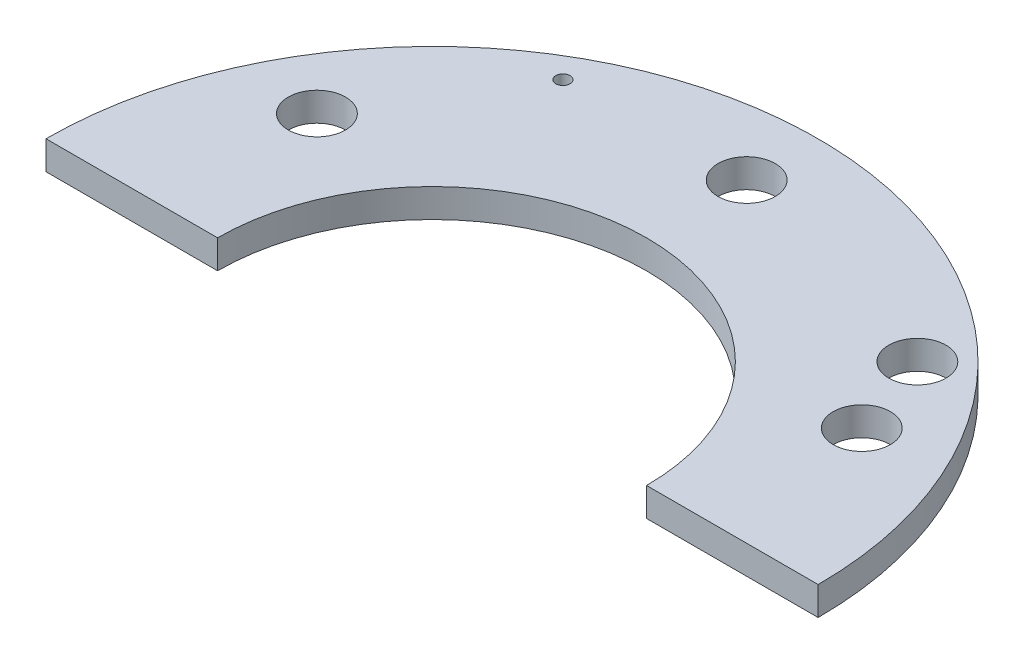
SolidWorks part; units mm, degrees
material "ABS"
ref_plane "Front Plane" through (0, 0, 0) normal (0, 0, 1) x (1, 0, 0)
ref_plane "Top Plane" through (0, 0, 0) normal (0, 1, 0) x (1, 0, 0)
ref_plane "Right Plane" through (0, 0, 0) normal (1, 0, 0) x (0, 0, -1)
sketch "Sketch1" plane through (0, 0, 0) normal (0, 1, 0) x (1, 0, 0)
  circle A0 centre (0, 0) radius 13.5
  dimension "D1" = 27
extrude "Boss-Extrude1" add sketch "Sketch1" along normal blind 1
sketch "Sketch19" plane through (0, 1, 0) normal (0, 1, 0) x (1, 0, 0)
  circle A0 centre (0, 11) radius 1
  circle A1 centre (9.5263, 5.5) radius 1
  circle A2 centre (9.5263, -5.5) radius 1
  circle A3 centre (0, -11) radius 1
  circle A4 centre (-9.5263, -5.5) radius 1
  circle A5 centre (-9.5263, 5.5) radius 1
  point P13 (0, 0)
  dimension "D1" = 2
  dimension "D2" = 11
  dimension "D3" = 6
extrude "Cut-Extrude1" cut sketch "Sketch19" against normal through all both and the other way through all
sketch "Sketch20" plane through (0, 1, 0) normal (0, 1, 0) x (1, 0, 0)
  circle A0 centre (0, 0) radius 7.5
  dimension "D1" = 15
extrude "Cut-Extrude2" cut sketch "Sketch20" against normal through all both and the other way through all
sketch "Sketch21" plane through (0, 0, 0) normal (0, 0, 1) x (1, 0, 0)
  line L1 (-36.7533, 32.3113) -> (29.1209, 32.3113)
  line L2 (-36.7533, 32.3113) -> (-36.7533, -19.668)
  line L3 (-36.7533, -19.668) -> (29.1209, -19.668)
  line L4 (29.1209, 32.3113) -> (29.1209, -19.668)
extrude "Cut-Extrude3" cut sketch "Sketch21" along normal through all
sketch "Sketch22" plane through (0, 1, 0) normal (0, 1, 0) x (1, 0, 0)
  line L0 (-9.5263, 5.5) -> (0, 11)
  line L1 (0, 0) -> (-6.25, 10.8253) construction
  circle A0 centre (-6.25, 10.8253) radius 0.25
  dimension "D1" = 0.5
  dimension "D2" = 12.5
extrude "Cut-Extrude4" cut sketch "Sketch22" against normal through all both and the other way through all contours A0 | A0 L1 | L1 A0 region at (-6.25, 1, -10.8253)
sketch "Sketch23" plane through (0, 1, 0) normal (0, 1, 0) x (1, 0, 0)
  line L0 (0, 0) -> (-6.25, 10.8253) construction
  line L1 (-6.25, 10.8253) -> (0, 0) construction
  line L2 (0, 0) -> (12.508, 12.508) construction
  circle A0 centre (8.4853, 8.4853) radius 1
  dimension "D1" = 2
  dimension "D2" = 12
  dimension "D3" = 75
extrude "Cut-Extrude5" cut sketch "Sketch23" against normal through all both and the other way through all
